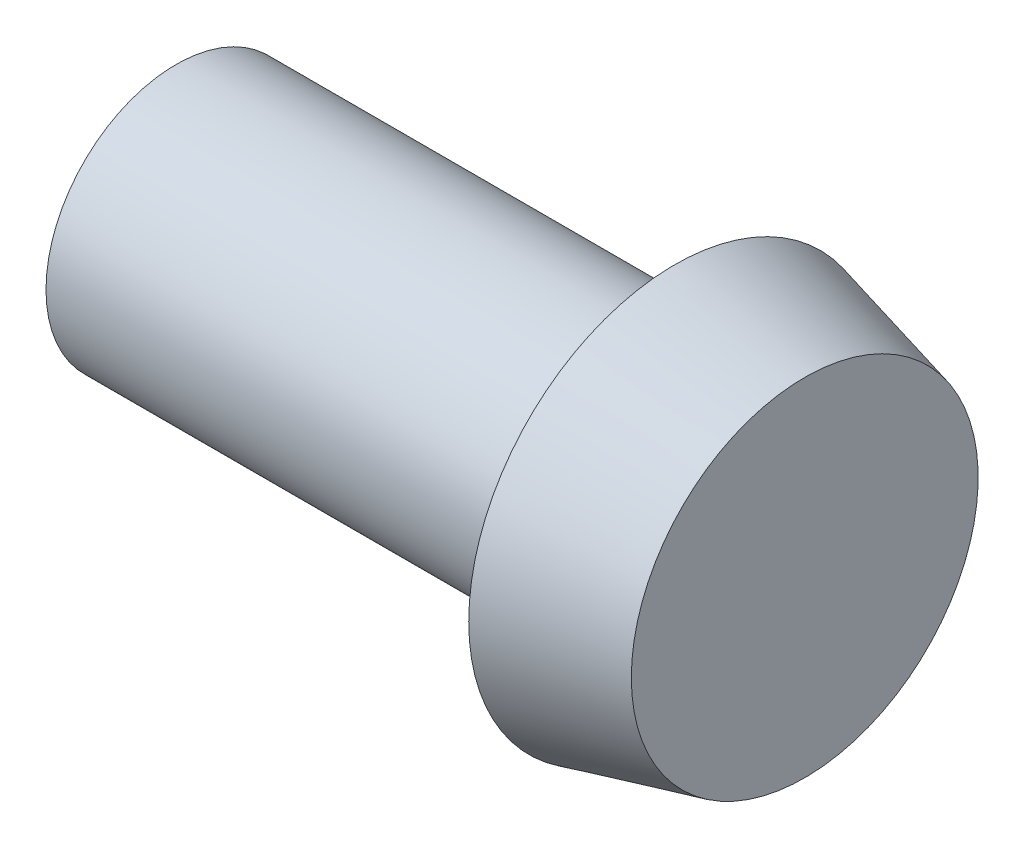
SolidWorks part; units mm, degrees
ref_plane "Front Plane" through (0, 0, 0) normal (0, 0, 1) x (1, 0, 0)
ref_plane "Top Plane" through (0, 0, 0) normal (0, 1, 0) x (1, 0, 0)
ref_plane "Right Plane" through (0, 0, 0) normal (1, 0, 0) x (0, 0, -1)
sketch "Sketch5" plane through (0, 0, 0) normal (0, 1, 0) x (1, 0, 0)
  line L4 (-30.465, 0) -> (22.1993, 0) construction
  line L12 (0, 6) -> (-23, 6)
  line L13 (0, 0) -> (6, 0)
  line L14 (6, 0) -> (6, 8)
  line L15 (0, 9.5) -> (6, 8)
  line L16 (0, 6) -> (0, 9.5)
  line L17 (-23, 6) -> (-23, 0)
  line L18 (-23, 0) -> (6, 0)
  dimension "D1" = 6
  dimension "D2" = 23
  dimension "D3" = 6
  dimension "D4" = 9.5
  dimension "D5" = 8
revolve "Revolve2" add sketch "Sketch5" angle 360 about L4
